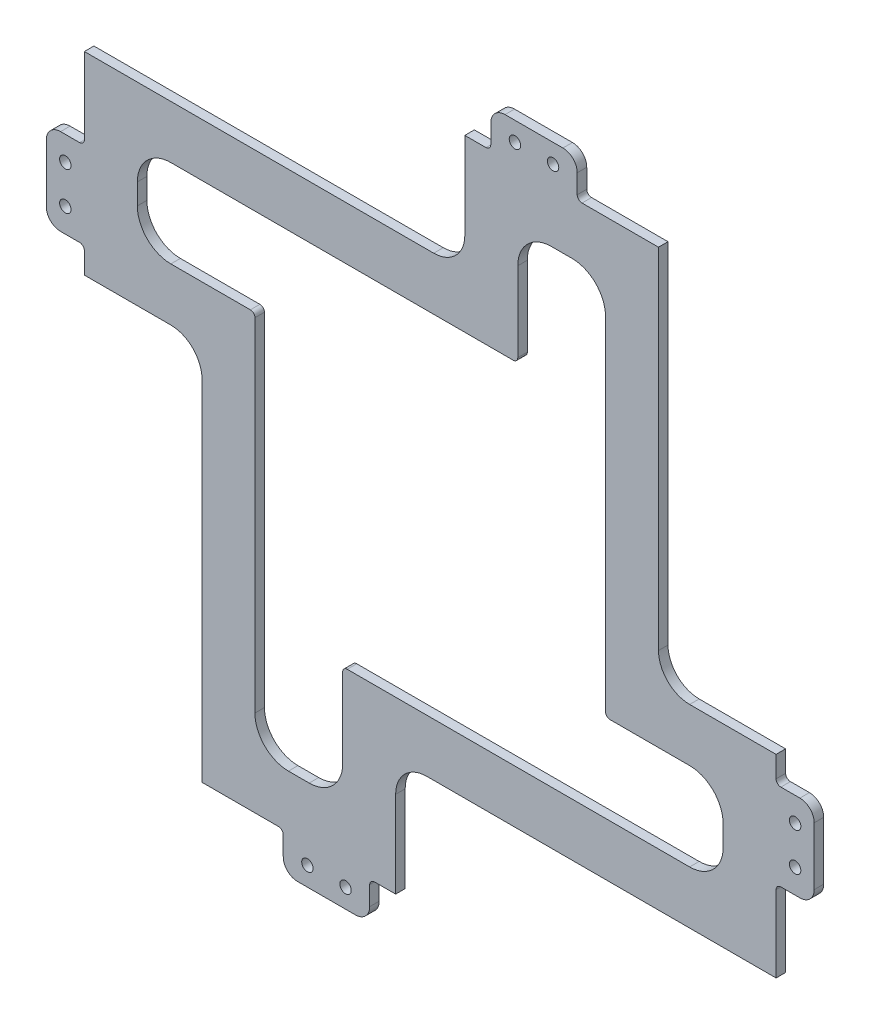
SolidWorks part; units mm, degrees
ref_plane "front" through (0, 0, 0) normal (0, 0, 1) x (1, 0, 0)
ref_plane "top" through (0, 0, 0) normal (0, 1, 0) x (1, 0, 0)
ref_plane "right" through (0, 0, 0) normal (1, 0, 0) x (0, 0, -1)
ref_axis "Axis1" through (0, 0, -69.7337) along (0, 0, 1)
sketch "Sketch1" plane through (0, 0, 0) normal (0, 0, 1) x (1, 0, 0)
  line L0 (-4.6101, 4.6101) -> (4.6101, 4.6101)
  line L1 (4.6101, 4.6101) -> (4.6101, -4.6101)
  line L2 (4.6101, -4.6101) -> (-4.6101, -4.6101)
  line L3 (-4.6101, -4.6101) -> (-4.6101, 4.6101)
  line L4 (-4.6101, 0) -> (-52.6937, 0) construction
  line L5 (-52.6937, 0) -> (0, 9.2913)
  line L6 (-52.6937, 0) -> (0, 4.6101)
  dimension "D1" = 10
  dimension "D2" = 5
  dimension "D3" = 52.6937
  dimension "D4" = 53.5066
  dimension "A" = 9.2202
sketch "Sketch2" plane through (0, 0, 0) normal (0, 0, 1) x (1, 0, 0)
  line L0 (-3.6881, 4.6101) -> (2.2128, 4.6101)
  line L1 (-4.6101, 4.6101) -> (4.6101, 4.6101) construction
  line L2 (2.3973, 4.7945) -> (2.3973, 6.9151)
  line L3 (4.6101, 6.9151) -> (4.6101, 1.844)
  line L4 (4.6101, 1.844) -> (6.0853, 1.844)
  line L5 (6.0853, 1.844) -> (6.0853, 9.2202)
  line L6 (1.4865, 9.2202) -> (0.922, 9.2202)
  line L7 (0.922, 6.9151) -> (2.3973, 6.9151) construction
  line L8 (0.922, 9.2202) -> (0.922, 6.9151)
  line L10 (6.0853, 9.2202) -> (4.0456, 9.2202)
  line L11 (3.9186, 9.3472) -> (3.9186, 9.8552)
  line L12 (3.5376, 10.2362) -> (1.9945, 10.2362)
  line L13 (1.6135, 9.8552) -> (1.6135, 9.3472)
  line L14 (0.0922, 6.0853) -> (-3.6881, 6.0853)
  line L15 (-3.6881, 6.0853) -> (-3.6881, 4.6101)
  line L16 (4.6101, 4.6101) -> (4.6101, -4.6101) construction
  line L18 (3.2271, 7.745) -> (3.7803, 7.745)
  arc A0 (0.922, 6.9151) -> (0.0922, 6.0853) centre (0.0922, 6.9151) cw
  arc A1 (1.9945, 10.2362) -> (1.6135, 9.8552) centre (1.9945, 9.8552) ccw
  arc A2 (3.9186, 9.8552) -> (3.5376, 10.2362) centre (3.5376, 9.8552) ccw
  arc A3 (1.6135, 9.3472) -> (1.4865, 9.2202) centre (1.4865, 9.3472) cw
  circle A4 centre (3.2741, 9.7282) radius 0.1524
  arc A5 (4.0456, 9.2202) -> (3.9186, 9.3472) centre (4.0456, 9.3472) cw
  circle A6 centre (2.2581, 9.7282) radius 0.1524
  arc A9 (3.7803, 7.745) -> (4.6101, 6.9151) centre (3.7803, 6.9151) cw
  arc A10 (2.3973, 6.9151) -> (3.2271, 7.745) centre (3.2271, 6.9151) cw
  arc A11 (2.2128, 4.6101) -> (2.3973, 4.7945) centre (2.2128, 4.7945) ccw
  point P16 (2.7661, 10.2362)
  dimension "D9" = 0.1844
  dimension "D6" = 0.127
  dimension "D14" = 0.3048
  dimension "D2" = 4.6101
  dimension "D5" = 2.3051
  dimension "D8" = 1.4752
  dimension "D10" = 1.4752
  dimension "D12" = 3.6881
  dimension "D13" = 1.844
  dimension "D4" = 0.922
  dimension "D15" = 5.1633
  dimension "D11" = 2.7661
  dimension "D18" = 0.508
extrude "Extrude1" add sketch "Sketch2" against normal mid plane 0.254
pattern_circular "CirPattern1" count 4 over 360 about axis through (0, 0, -69.7337) along (0, 0, 1) of "Extrude1"
sketch "Sketch3" plane through (0, 0, 0.127) normal (0, 0, 1) x (1, 0, 0)
  line L167 (-7.8085, 3.7803) -> (-7.8085, 3.2271)
  line L168 (-6.9152, 2.3338) -> (-4.7945, 2.3338)
  line L169 (-4.6736, 2.2128) -> (-4.6736, -6.9152)
  line L170 (-3.7803, -7.8085) -> (-3.2271, -7.8085)
  line L171 (-2.3338, -6.9152) -> (-2.3338, -4.7945)
  line L172 (-2.2128, -4.6736) -> (6.9152, -4.6736)
  line L173 (7.8085, -3.7803) -> (7.8085, -3.2271)
  line L174 (6.9152, -2.3338) -> (4.7945, -2.3338)
  line L175 (4.6736, -2.2128) -> (4.6736, 6.9151)
  line L176 (3.7803, 7.8085) -> (3.2271, 7.8085)
  line L177 (2.3338, 6.9151) -> (2.3338, 4.7945)
  line L178 (2.2128, 4.6736) -> (-6.9152, 4.6736)
  line L179 (-7.8085, 3.7803) -> (-7.8085, 3.2271)
  line L180 (-6.9152, 2.3338) -> (-4.7945, 2.3338)
  line L181 (-4.6736, 2.2128) -> (-4.6736, -6.9152)
  line L182 (-3.7803, -7.8085) -> (-3.2271, -7.8085)
  line L183 (-2.3338, -6.9152) -> (-2.3338, -4.7945)
  line L184 (-2.2128, -4.6736) -> (6.9152, -4.6736)
  line L185 (7.8085, -3.7803) -> (7.8085, -3.2271)
  line L186 (6.9152, -2.3338) -> (4.7945, -2.3338)
  line L187 (4.6736, -2.2128) -> (4.6736, 6.9151)
  line L188 (3.7803, 7.8085) -> (3.2271, 7.8085)
  line L189 (2.3338, 6.9151) -> (2.3338, 4.7945)
  line L190 (2.2128, 4.6736) -> (-6.9152, 4.6736)
  arc A157 (-6.9152, 4.6736) -> (-7.8085, 3.7803) centre (-6.9152, 3.7803) ccw
  arc A158 (-7.8085, 3.2271) -> (-6.9152, 2.3338) centre (-6.9152, 3.2271) ccw
  arc A159 (-4.6736, 2.2128) -> (-4.7945, 2.3338) centre (-4.7945, 2.2128) ccw
  arc A160 (-4.6736, -6.9152) -> (-3.7803, -7.8085) centre (-3.7803, -6.9152) ccw
  arc A161 (-3.2271, -7.8085) -> (-2.3338, -6.9152) centre (-3.2271, -6.9152) ccw
  arc A162 (-2.2128, -4.6736) -> (-2.3338, -4.7945) centre (-2.2128, -4.7945) ccw
  arc A163 (6.9152, -4.6736) -> (7.8085, -3.7803) centre (6.9152, -3.7803) ccw
  arc A164 (7.8085, -3.2271) -> (6.9152, -2.3338) centre (6.9152, -3.2271) ccw
  arc A165 (4.6736, -2.2128) -> (4.7945, -2.3338) centre (4.7945, -2.2128) ccw
  arc A166 (4.6736, 6.9151) -> (3.7803, 7.8085) centre (3.7803, 6.9151) ccw
  arc A167 (3.2271, 7.8085) -> (2.3338, 6.9151) centre (3.2271, 6.9151) ccw
  arc A168 (2.2128, 4.6736) -> (2.3338, 4.7945) centre (2.2128, 4.7945) ccw
  arc A169 (-6.9152, 4.6736) -> (-7.8085, 3.7803) centre (-6.9152, 3.7803) ccw
  arc A170 (-7.8085, 3.2271) -> (-6.9152, 2.3338) centre (-6.9152, 3.2271) ccw
  arc A171 (-4.6736, 2.2128) -> (-4.7945, 2.3338) centre (-4.7945, 2.2128) ccw
  arc A172 (-4.6736, -6.9152) -> (-3.7803, -7.8085) centre (-3.7803, -6.9152) ccw
  arc A173 (-3.2271, -7.8085) -> (-2.3338, -6.9152) centre (-3.2271, -6.9152) ccw
  arc A174 (-2.2128, -4.6736) -> (-2.3338, -4.7945) centre (-2.2128, -4.7945) ccw
  arc A175 (6.9152, -4.6736) -> (7.8085, -3.7803) centre (6.9152, -3.7803) ccw
  arc A176 (7.8085, -3.2271) -> (6.9152, -2.3338) centre (6.9152, -3.2271) ccw
  arc A177 (4.6736, -2.2128) -> (4.7945, -2.3338) centre (4.7945, -2.2128) ccw
  arc A178 (4.6736, 6.9151) -> (3.7803, 7.8085) centre (3.7803, 6.9151) ccw
  arc A179 (3.2271, 7.8085) -> (2.3338, 6.9151) centre (3.2271, 6.9151) ccw
  arc A180 (2.2128, 4.6736) -> (2.3338, 4.7945) centre (2.2128, 4.7945) ccw
  dimension "D1" = 0.0635
extrude "Cut-Extrude1" cut sketch "Sketch3" against normal blind 0.381
equation "\"D2@Sketch2\" = .5 * \"A\""
equation "\"D13@Sketch2\" = .2 * \"A\""
equation "\"D8@Sketch2\" = .16 * \"A\""
equation "\"D10@Sketch2\" = .16 * \"A\""
equation "\"D5@Sketch2\" = .25 * \"A\""
equation "\"D12@Sketch2\" = .4 * \"A\""
equation "\"D4@Sketch2\"=.1*\"A\""
equation "\"D9@Sketch2\"=.02*\"A\""
equation "\"D11@Sketch2\"=.3*\"A\""
